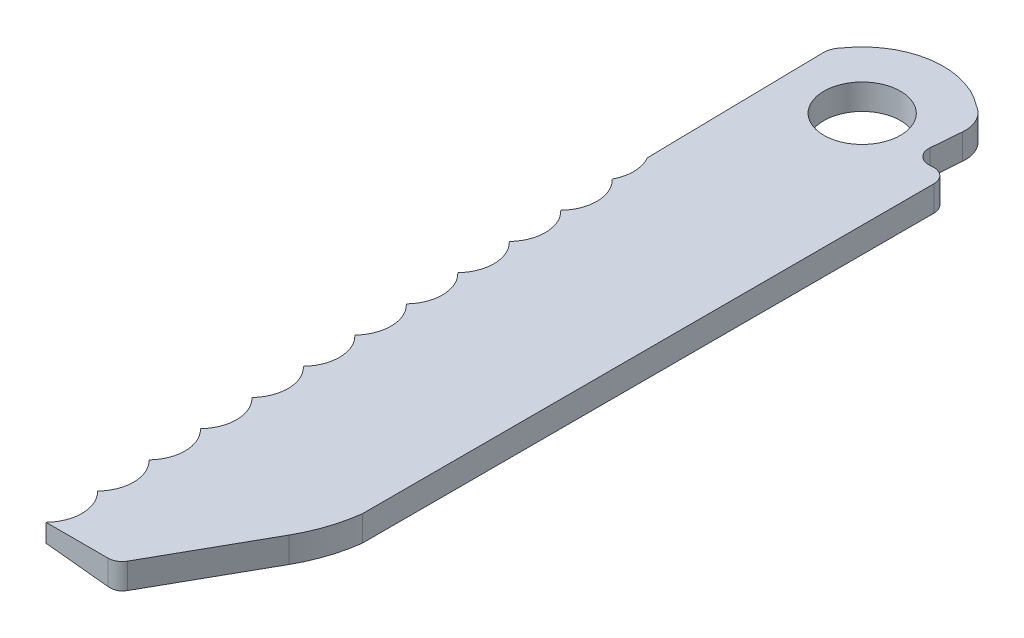
SolidWorks part; units mm, degrees
material "Plain Carbon Steel"
ref_plane "Front Plane" through (0, 0, 0) normal (0, 0, 1) x (1, 0, 0)
ref_plane "Top Plane" through (0, 0, 0) normal (0, 1, 0) x (1, 0, 0)
ref_plane "Right Plane" through (0, 0, 0) normal (1, 0, 0) x (0, 0, -1)
sketch "Sketch1" plane through (0, 0, 0) normal (0, 1, 0) x (1, 0, 0)
  line L0 (16.7853, 37.7669) -> (83.9265, 37.7669) construction
  line L1 (58.5595, 61.2582) -> (58.3532, 58.7408)
  line L2 (60.2335, 26.7373) -> (60.2335, 58.807)
  line L3 (58.3532, 58.7408) -> (60.2335, 58.807)
  line L4 (59.2323, 23.7058) -> (55.8327, 17.6675)
  line L5 (51.983, 17.6675) -> (55.8327, 17.6675)
  line L6 (50.9908, 61.1729) -> (51.1623, 51.4011)
  line L7 (51.1623, 51.4011) -> (51.983, 17.6675) construction
  arc A0 (51.2963, 61.9533) -> (57.6891, 62.876) centre (54.9292, 59.3902) cw
  arc A1 (51.2963, 61.9533) -> (50.9908, 61.1729) centre (52.0909, 61.1922) ccw
  arc A2 (57.6891, 62.876) -> (58.5595, 61.2582) centre (56.8772, 61.3961) cw
  arc A3 (60.2335, 26.7373) -> (59.2323, 23.7058) centre (52.0096, 27.7723) cw
  arc A4 (51.1623, 51.4011) -> (51.2102, 49.4312) centre (49.4031, 50.3728) cw
  arc A5 (51.9128, 20.5551) -> (51.983, 17.6675) centre (50.5108, 19.0764) cw
  arc A6 (51.9128, 20.5551) -> (51.8425, 23.4427) centre (50.4405, 21.964) ccw
  arc A7 (51.7722, 26.3303) -> (51.8425, 23.4427) centre (50.3703, 24.8516) cw
  arc A8 (51.7722, 26.3303) -> (51.702, 29.218) centre (50.3, 27.7392) ccw
  arc A9 (51.6317, 32.1056) -> (51.702, 29.218) centre (50.2298, 30.6268) cw
  arc A10 (51.6317, 32.1056) -> (51.5615, 34.9932) centre (50.1595, 33.5144) ccw
  arc A11 (51.4912, 37.8808) -> (51.5615, 34.9932) centre (50.0893, 36.402) cw
  arc A12 (51.421, 40.7684) -> (51.4912, 37.8808) centre (50.019, 39.2896) cw
  arc A13 (51.421, 40.7684) -> (51.3507, 43.656) centre (49.9488, 42.1772) ccw
  arc A14 (51.2102, 49.4312) -> (51.2805, 46.5436) centre (49.8082, 47.9525) cw
  arc A15 (51.2805, 46.5436) -> (51.3507, 43.656) centre (49.8785, 45.0648) cw
  circle A16 centre (54.9292, 59.3902) radius 2.0955
  dimension "D1" = 4.191
  dimension "D3" = 4.4461
  dimension "D7" = 6.9295
  dimension "D8" = 3.8497
  dimension "D9" = 32.0697
  dimension "D10" = 1.1003
  dimension "D11" = 1.6879
  dimension "D12" = 2.0377
  dimension "D13" = 8.2888
  dimension "D14" = 49.4031
  dimension "D15" = 52.0096
  dimension "D16" = 56.8772
  dimension "D2" = 1.005
  dimension "D4" = 1.8804
  dimension "D5" = 2.5258
  dimension "D6" = 43.5054
  dimension "D17" = 58.3532
  dimension "D28" = 51.2963
  dimension "D39" = 54.9292
  dimension "D41" = 57.6891
extrude "Boss-Extrude1" add sketch "Sketch1" along normal blind 1.397
sketch "Sketch2" plane through (0, 0, 0) normal (0, 0, 1) x (1, 0, 0)
  line L0 (55.8327, 0) -> (50.9908, 0.5089)
  line L1 (50.9908, 1.397) -> (50.9908, 0) construction
  line L2 (50.9908, 0.5089) -> (50.9908, 0)
  line L3 (50.9908, 0) -> (55.8327, 0)
  dimension "D1" = 6
extrude "Cut-Extrude1" cut sketch "Sketch2" against normal blind 52.451
fillet "Fillet1" radius 0.762 3 edges at (60.2335, 0.6985, -58.807) (58.3532, 0.6985, -58.7408) (55.8327, 0.6985, -17.6675)
